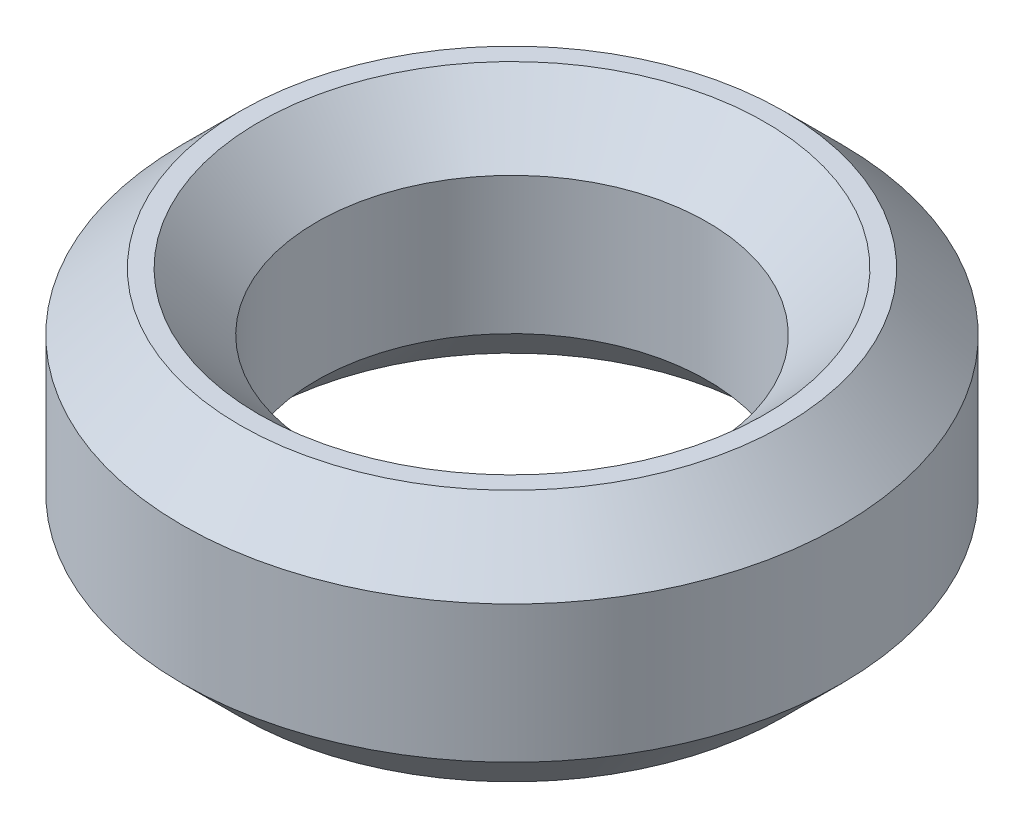
SolidWorks part; units mm, degrees
ref_plane "Front Plane" through (0, 0, 0) normal (0, 0, 1) x (1, 0, 0)
ref_plane "Top Plane" through (0, 0, 0) normal (0, 1, 0) x (1, 0, 0)
ref_plane "Right Plane" through (0, 0, 0) normal (1, 0, 0) x (0, 0, -1)
sketch "Sketch1" plane through (0, 0, 0) normal (0, 1, 0) x (1, 0, 0)
  circle A0 centre (0, 0) radius 17.5
  dimension "SLEEVE_OD" = 35
extrude "Boss-Extrude1" add sketch "Sketch1" along normal blind 13.4016
sketch "Sketch2" plane through (0, 0, 0) normal (0, 1, 0) x (1, 0, 0)
  circle A0 centre (0, 0) radius 10.3712
  dimension "BORE_D" = 20.7423
extrude "Cut-Extrude1" cut sketch "Sketch2" along normal through all
chamfer "Chamfer1" distance 3.0631 angle 45 4 edges at (0, 13.4016, 10.3712) (0, 0, 10.3712) (0, 0, 17.5) (0, 13.4016, 17.5)
